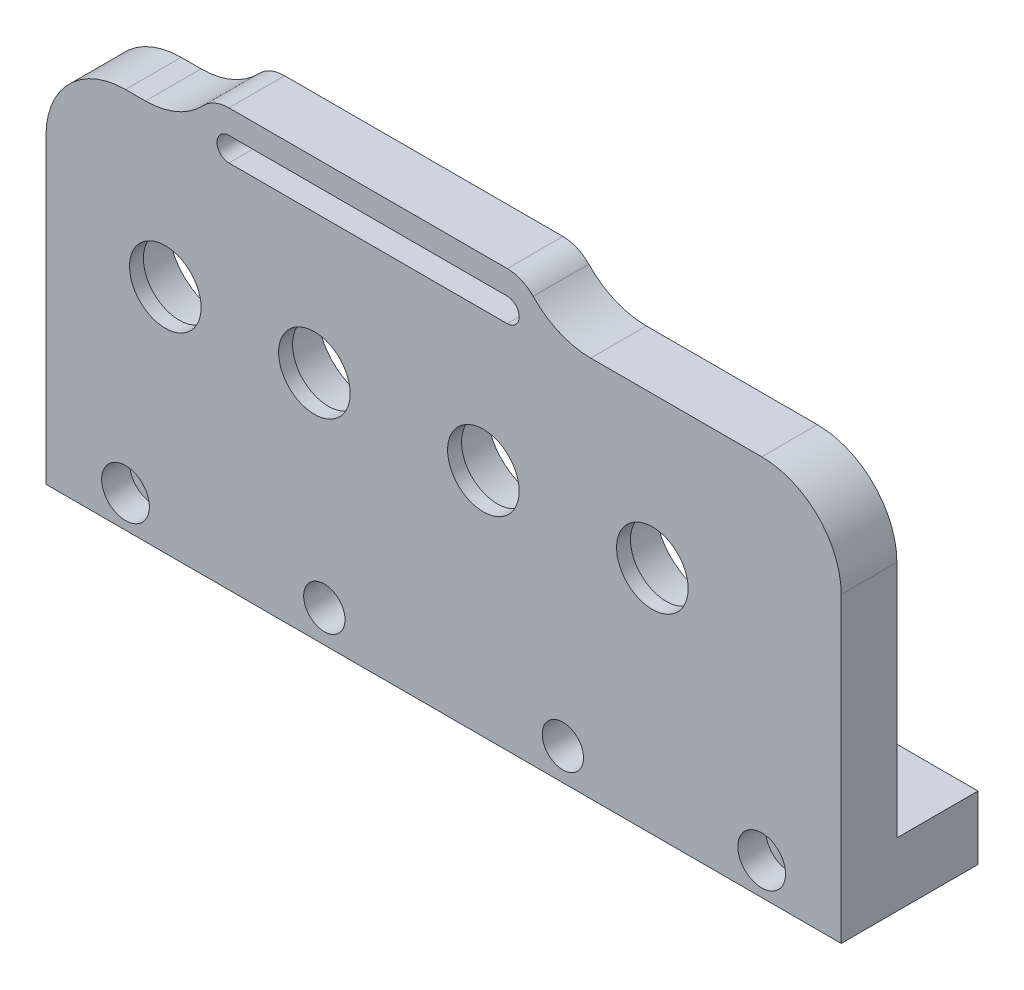
SolidWorks part; units mm, degrees
ref_plane "Front Plane" through (0, 0, 0) normal (0, 0, 1) x (1, 0, 0)
ref_plane "Top Plane" through (0, 0, 0) normal (0, 1, 0) x (1, 0, 0)
ref_plane "Right Plane" through (0, 0, 0) normal (1, 0, 0) x (0, 0, -1)
sketch "Sketch1" plane through (0, 0, 0) normal (0, 0, 1) x (1, 0, 0)
  line L1 (0, 0) -> (100, 0)
  line L2 (0, 0) -> (0, 48)
  line L3 (0, 48) -> (100, 48)
  line L4 (100, 0) -> (100, 48)
  dimension "D1" = 100
  dimension "D2" = 48
extrude "Boss-Extrude1" add sketch "Sketch1" along normal blind 7
sketch "Sketch2" plane through (0, 0, 7) normal (0, 0, 1) x (1, 0, 0)
  line L0 (0, 0) -> (100, 0) construction
  line L1 (0, 48) -> (0, 0) construction
  circle A0 centre (15, 29) radius 4.5
  circle A1 centre (33.75, 29) radius 4.5
  circle A2 centre (55, 29) radius 4.5
  circle A3 centre (76.25, 29) radius 4.5
  dimension "D1" = 9
  dimension "D7" = 9
  dimension "D2" = 18.75
  dimension "D3" = 21.25
  dimension "D4" = 21.25
  dimension "D5" = 29
  dimension "D6" = 15
extrude "Cut-Extrude1" cut sketch "Sketch2" against normal up to next
sketch "Sketch3" plane through (0, 0, 0) normal (0, 0, -1) x (-1, 0, 0)
  line L0 (0, 48) -> (0, 0) construction
  line L1 (-100, 0) -> (0, 0)
  line L2 (-100, 0) -> (-100, 8)
  line L3 (-100, 8) -> (0, 8)
  line L4 (0, 0) -> (0, 8)
  dimension "D1" = 8
extrude "Boss-Extrude2" add sketch "Sketch3" along normal blind 10.2
sketch "Sketch4" plane through (0, 0, 0) normal (0, 0, -1) x (-1, 0, 0)
  circle A0 centre (-76.25, 29) radius 6.6
  circle A1 centre (-55, 29) radius 6.6
  circle A2 centre (-33.75, 29) radius 6.6
  circle A3 centre (-15, 29) radius 6.6
  dimension "D1" = 13.2
extrude "Cut-Extrude2" cut sketch "Sketch4" against normal blind 5.25
sketch "Sketch5" plane through (0, 0, 7) normal (0, 0, 1) x (1, 0, 0)
  line L0 (35, 4.0521) -> (65, 4) construction
  line L1 (0, 0) -> (100, 0) construction
  circle A0 centre (35, 4.0521) radius 2.6
  circle A1 centre (65, 4) radius 2.6
  point P6 (50, 0)
  point P7 (50, 4.0261)
  dimension "D1" = 5.2
  dimension "D2" = 30
  dimension "D3" = 4
extrude "Cut-Extrude3" cut sketch "Sketch5" against normal blind 7
sketch "Sketch7" plane through (0, 0, 0) normal (0, 0, 1) x (1, 0, 0)
  circle A0 centre (35, 4.0521) radius 1.5
  circle A1 centre (65, 4) radius 1.5
  dimension "D1" = 3
extrude "Cut-Extrude4" cut sketch "Sketch7" against normal through all
sketch "Sketch8" plane through (0, 0, 7) normal (0, 0, 1) x (1, 0, 0)
  line L0 (10, 4.0521) -> (35, 4.0521) construction
  line L1 (0, 48) -> (0, 0) construction
  line L2 (100, 0) -> (100, 48) construction
  circle A0 centre (10, 4.0521) radius 1.7
  circle A1 centre (90, 4.0521) radius 1.7
  dimension "D1" = 3.4
  dimension "D2" = 10
  dimension "D3" = 10
extrude "Cut-Extrude5" cut sketch "Sketch8" against normal up to next
sketch "Sketch9" plane through (0, 0, 7) normal (0, 0, 1) x (1, 0, 0)
  circle A0 centre (10, 4.0521) radius 3
  circle A1 centre (90, 4.0521) radius 3
  dimension "D1" = 6
extrude "Cut-Extrude6" cut sketch "Sketch9" against normal blind 3.5
sketch "Sketch10" plane through (0, 0, 7) normal (0, 0, 1) x (1, 0, 0)
  line L0 (23, 48) -> (58, 48) construction
  line L1 (100, 48) -> (0, 48) construction
  line L2 (23, 49.5) -> (58, 49.5)
  line L3 (23, 46.5) -> (58, 46.5)
  line L4 (23, 52.5) -> (58, 52.5)
  line L5 (23, 43.5) -> (58, 43.5)
  line L6 (0, 48) -> (0, 0) construction
  arc A0 (23, 49.5) -> (23, 46.5) centre (23, 48) ccw
  arc A1 (58, 46.5) -> (58, 49.5) centre (58, 48) ccw
  arc A2 (58, 43.5) -> (58, 52.5) centre (58, 48) ccw
  arc A3 (23, 52.5) -> (23, 43.5) centre (23, 48) ccw
  point P4 (40.5, 48)
  dimension "D3" = 35
  dimension "D2" = 3
  dimension "D4" = 23
  dimension "D1" = 3
extrude "Boss-Extrude3" add sketch "Sketch10" against normal up to surface (7 mm away) up to face at (69.65, 29, 0)
sketch "Sketch11" plane through (0, 0, 7) normal (0, 0, 1) x (1, 0, 0)
  line L0 (23, 48) -> (58, 48) construction
  line L1 (59.5, 48) -> (21.5, 48) construction
  line L2 (23, 49.5) -> (58, 49.5)
  line L3 (23, 46.5) -> (58, 46.5)
  arc A0 (23, 49.5) -> (23, 46.5) centre (23, 48) ccw
  arc A1 (58, 46.5) -> (58, 49.5) centre (58, 48) ccw
  point P5 (40.5, 48)
  dimension "D1" = 3
extrude "Cut-Extrude7" cut sketch "Sketch11" against normal up to next
fillet "Fillet1" radius 10 2 edges at (0, 48, 3.5) (100, 48, 3.5)
fillet "Fillet2" radius 10 2 edges at (62.5, 48, 3.5) (18.5, 48, 3.5)
equation "\"D1@Sketch2\"=\"D7@Sketch2\""
